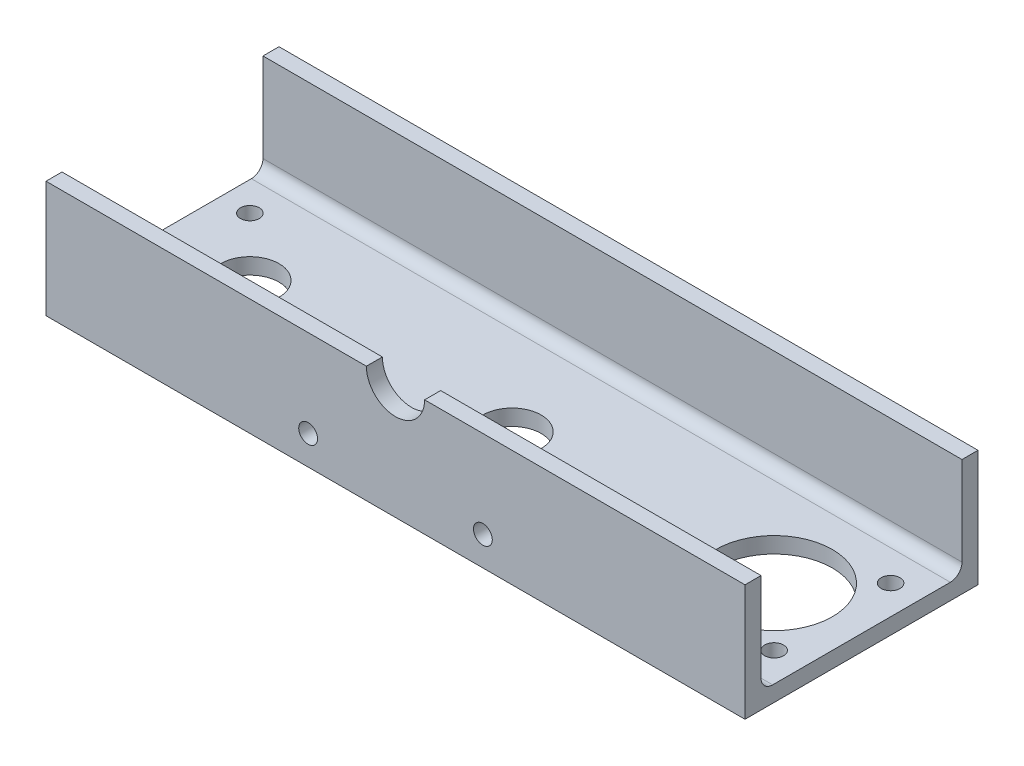
SolidWorks part; units mm, degrees
ref_plane "Front Plane" through (0, 0, 0) normal (0, 0, 1) x (1, 0, 0)
ref_plane "Top Plane" through (0, 0, 0) normal (0, 1, 0) x (1, 0, 0)
ref_plane "Right Plane" through (0, 0, 0) normal (1, 0, 0) x (0, 0, -1)
sketch "Sketch1" plane through (0, 0, 0) normal (1, 0, 0) x (0, 0, -1)
  line L0 (-21.9075, 9.2075) -> (21.9075, 9.2075)
  line L1 (-25.4, -12.7) -> (25.4, -12.7)
  line L2 (-25.4, -12.7) -> (-25.4, 12.7)
  line L3 (-25.4, 12.7) -> (25.4, 12.7)
  line L4 (25.4, -12.7) -> (25.4, 12.7)
  line L5 (-25.4, -12.7) -> (25.4, 12.7) construction
  line L6 (-25.4, 12.7) -> (25.4, -12.7) construction
  line L7 (21.9075, -6.6675) -> (21.9075, 9.2075)
  line L8 (-19.3675, -9.2075) -> (19.3675, -9.2075)
  line L9 (-21.9075, -6.6675) -> (-21.9075, 9.2075)
  line L10 (-21.9075, 9.2075) -> (-21.9075, 12.7)
  line L11 (21.9075, 9.2075) -> (21.9075, 12.7)
  line L12 (21.9075, -9.2075) -> (21.9075, 9.2075) construction
  line L13 (-21.9075, -9.2075) -> (21.9075, -9.2075) construction
  line L14 (-21.9075, -9.2075) -> (-21.9075, 9.2075) construction
  arc A0 (21.9075, -6.6675) -> (19.3675, -9.2075) centre (19.3675, -6.6675) cw
  arc A1 (-19.3675, -9.2075) -> (-21.9075, -6.6675) centre (-19.3675, -6.6675) cw
  point P0 (0, 0)
  dimension "D4" = 2.54
  dimension "D1" = 25.4
  dimension "D2" = 50.8
  dimension "D3" = 3.4925
extrude "Boss-Extrude1" add sketch "Sketch1" against normal blind 152.4 contours L8 A1 L9 L10 L3 L2 L1 L4 L11 L7 A0 region at (0, 1.27, 22.4755)
sketch "Sketch2" plane through (0, 0, 25.4) normal (0, 0, 1) x (1, 0, 0)
  line L0 (-152.4, 12.7) -> (0, 12.7) construction
  circle A0 centre (-76.2, 12.7) radius 6.35
  circle A3 centre (-57.15, -6.35) radius 2.05
  circle A4 centre (-95.25, -6.35) radius 2.05
  dimension "D1" = 12.7
extrude "Cut-Extrude1" cut sketch "Sketch2" against normal blind 6.35
sketch "Sketch4" plane through (0, -12.7, 0) normal (0, -1, 0) x (1, 0, 0)
  circle A11 centre (-133.35, 0) radius 6.35
  circle A12 centre (-76.2, 0) radius 6.35
  circle A13 centre (-19.05, 0) radius 12.7
  circle A18 centre (-146.05, 12.7) radius 2.05
  circle A19 centre (-146.05, -12.7) radius 2.05
  circle A20 centre (-6.35, -12.7) radius 2.05
  circle A21 centre (-6.35, 12.7) radius 2.05
  dimension "D1" = 25.4
extrude "Cut-Extrude2" cut sketch "Sketch4" against normal blind 6.35
